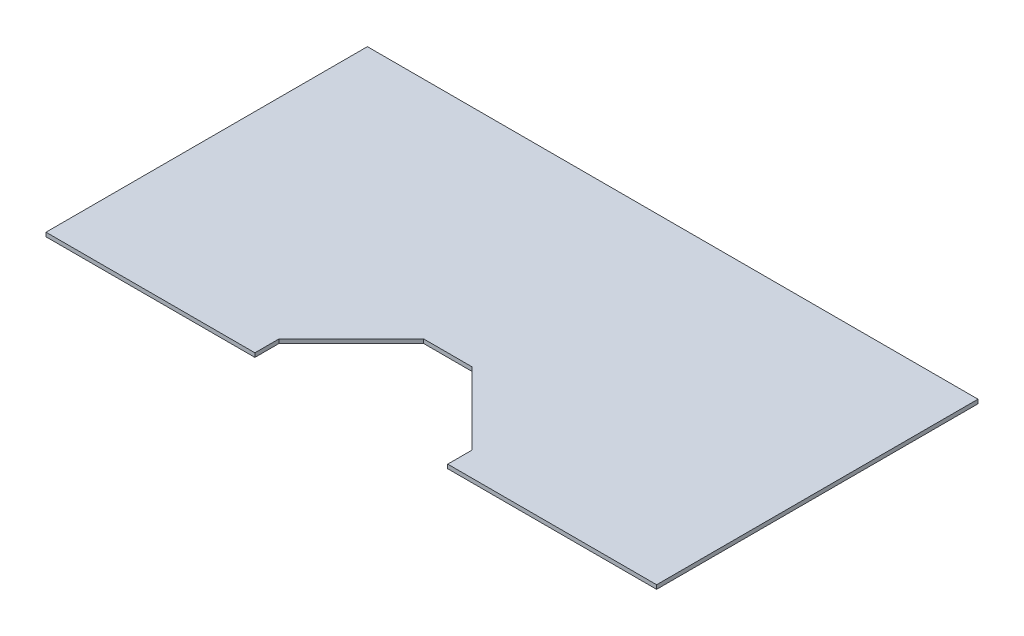
SolidWorks part; units mm, degrees
ref_plane "Front Plane" through (0, 0, 0) normal (0, 0, 1) x (1, 0, 0)
ref_plane "Top Plane" through (0, 0, 0) normal (0, 1, 0) x (1, 0, 0)
ref_plane "Right Plane" through (0, 0, 0) normal (1, 0, 0) x (0, 0, -1)
sketch "Sketch1" plane through (0, 0, 0) normal (0, 1, 0) x (1, 0, 0)
  line L0 (165.1, 0) -> (165.1, 76.2)
  line L1 (0, 0) -> (165.1, 0)
  line L2 (0, 0) -> (0, 254)
  line L3 (0, 254) -> (482.6, 254)
  line L4 (482.6, 0) -> (482.6, 254)
  line L5 (165.1, 76.2) -> (317.5, 76.2)
  line L6 (317.5, 76.2) -> (317.5, 0)
  line L7 (241.3, 254) -> (241.3, 76.2) construction
  line L8 (317.5, 0) -> (482.6, 0)
  dimension "D3" = 76.2
  dimension "D4" = 152.4
  dimension "D1" = 254
  dimension "D2" = 482.6
extrude "Boss-Extrude1" add sketch "Sketch1" along normal blind 3.175
chamfer "Chamfer1" distance 57.15 angle 45 2 edges at (317.5, 1.5875, -76.2) (165.1, 1.5875, -76.2) tangent propagation no
